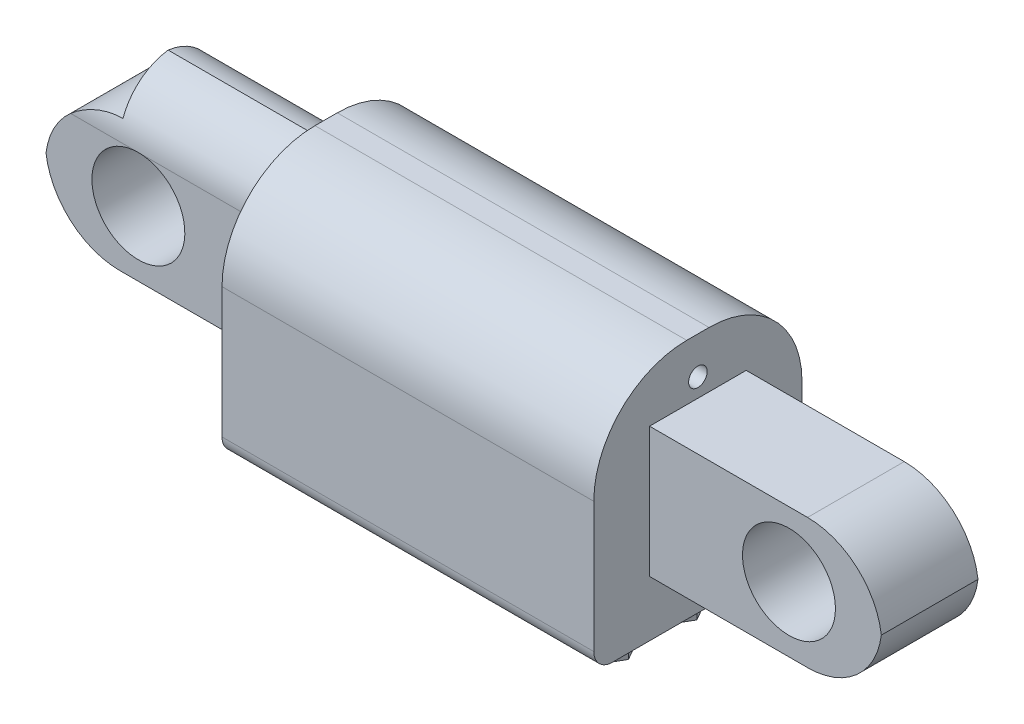
SolidWorks part; units mm, degrees
material "PLA"
ref_plane "Front" through (0, 0, 0) normal (0, 0, 1) x (1, 0, 0)
ref_plane "Top" through (0, 0, 0) normal (0, 1, 0) x (1, 0, 0)
ref_plane "Right" through (0, 0, 0) normal (1, 0, 0) x (0, 0, -1)
sketch "Sketch1" plane through (0, 0, 0) normal (0, 0, 1) x (1, 0, 0)
  line L1 (-6.35, 4.445) -> (9.525, 4.445)
  line L2 (-6.35, 4.445) -> (-6.35, -4.445)
  line L3 (-6.35, -4.445) -> (9.525, -4.445)
  line L4 (9.525, 4.445) -> (9.525, -4.445)
  circle A0 centre (0, 0) radius 3.175
  dimension "D1" = 6.35
  dimension "D2" = 6.35
  dimension "D3" = 4.445
  dimension "D4" = 4.445
  dimension "D5" = 15.875
extrude "Boss-Extrude1" add sketch "Sketch1" along normal blind 6.604
fillet "Fillet1" radius 5.08 2 edges at (-6.35, -4.445, 3.302) (-6.35, 4.445, 3.302)
sketch "Sketch2" plane through (9.525, 0, 0) normal (1, 0, 0) x (0, 0, -1)
  line L0 (-10.414, -8.255) -> (3.81, -8.255)
  line L1 (3.81, -8.255) -> (3.81, 8.255)
  line L2 (3.81, 8.255) -> (-10.414, 8.255)
  line L3 (-10.414, 8.255) -> (-10.414, -8.255)
  line L4 (0, -4.445) -> (0, 4.445)
  line L5 (0, 4.445) -> (-6.604, 4.445)
  line L6 (-6.604, 4.445) -> (-6.604, -4.445)
  line L7 (-6.604, -4.445) -> (0, -4.445)
  line L8 (0, -4.445) -> (0, 4.445)
  line L9 (0, 4.445) -> (-6.604, 4.445)
  line L10 (-6.604, 4.445) -> (-6.604, -4.445)
  line L11 (-6.604, -4.445) -> (0, -4.445)
  line M5 (0, -4.445) -> (0, 4.445)
  line M6 (0, 4.445) -> (-6.604, 4.445)
  line M7 (-6.604, 4.445) -> (-6.604, -4.445)
  line M8 (-6.604, -4.445) -> (0, -4.445)
  dimension "D1" = 0
  dimension "D2" = 3.81
extrude "Boss-Extrude2" add sketch "Sketch2" along normal blind 25.4 separate body contours L2 L3 L0 L1 M5 M8 M7 M6 | M8 M5 M6 M7 region at (9.525, 0, 10.1961) region at (9.525, 0, 3.302)
ref_plane "Plane1" through (22.225, 0, 0) normal (-1, 0, 0) x (0, 0, 1)
mirror "Mirror7" about plane through (22.225, 0, 0) normal (-1, 0, 0) of bodies 101
fillet "Fillet3" radius 6.35 2 edges at (22.225, 8.255, -3.81) (22.225, 8.255, 10.414)
sketch "Sketch3" plane through (0, 4.445, 0) normal (0, 1, 0) x (1, 0, 0)
  line L4 (9.525, 0) -> (-1.27, 0)
  line L5 (-1.27, 0) -> (-1.27, -6.604)
  line L6 (-1.27, -6.604) -> (9.525, -6.604)
  line L7 (9.525, -6.604) -> (9.525, 0)
  line L12 (9.525, 0) -> (-1.27, 0)
  line L13 (-1.27, 0) -> (-1.27, -6.604)
  line L14 (-1.27, -6.604) -> (9.525, -6.604)
  line L15 (9.525, -6.604) -> (9.525, 0)
  dimension "D1" = 0
extrude "Boss-Extrude3" add sketch "Sketch3" along normal blind 2.54
sketch "Sketch4" plane through (-1.27, 0, 0) normal (-1, 0, 0) x (0, 0, 1)
  line L8 (6.604, 6.985) -> (6.604, 4.445) construction
  line L9 (0, 4.445) -> (6.604, 4.445) construction
  circle A0 centre (3.302, 5.715) radius 0.635
  dimension "D1" = 1.27
  dimension "D2" = 1.27
  dimension "D3" = 3.302
extrude "Cut-Extrude1" cut sketch "Sketch4" against normal through all
fillet "Fillet5" radius 3.81 2 edges at (4.1275, 6.985, 6.604) (4.1275, 6.985, 0)
fillet "Fillet6" radius 1.27 2 edges at (22.225, -8.255, -3.81) (22.225, -8.255, 10.414)
sketch "Sketch5" plane through (0, -8.255, 0) normal (0, -1, 0) x (1, 0, 0)
  line L0 (34.925, 2.667) -> (34.925, 3.937) construction
  line L1 (34.925, 9.144) -> (9.525, 9.144)
  line L2 (34.925, 9.144) -> (34.925, -2.54)
  line L3 (34.925, -2.54) -> (9.525, -2.54)
  line L4 (9.525, 9.144) -> (9.525, -2.54)
  line L5 (33.02, 6.9443) -> (34.29, 6.9443)
  line L6 (34.29, 6.9443) -> (34.925, 8.0441)
  line L7 (34.925, 8.0441) -> (34.29, 9.144)
  line L8 (34.29, 9.144) -> (33.02, 9.144)
  line L9 (33.02, 9.144) -> (32.385, 8.0441)
  line L10 (32.385, 8.0441) -> (33.02, 6.9443)
  line L11 (30.48, 6.9443) -> (31.75, 6.9443)
  line L12 (31.75, 6.9443) -> (32.385, 8.0441)
  line L13 (32.385, 8.0441) -> (31.75, 9.144)
  line L14 (31.75, 9.144) -> (30.48, 9.144)
  line L15 (30.48, 9.144) -> (29.845, 8.0441)
  line L16 (29.845, 8.0441) -> (30.48, 6.9443)
  line L17 (27.94, 6.9443) -> (29.21, 6.9443)
  line L18 (29.21, 6.9443) -> (29.845, 8.0441)
  line L19 (29.845, 8.0441) -> (29.21, 9.144)
  line L20 (29.21, 9.144) -> (27.94, 9.144)
  line L21 (27.94, 9.144) -> (27.305, 8.0441)
  line L22 (27.305, 8.0441) -> (27.94, 6.9443)
  line L23 (25.4, 6.9443) -> (26.67, 6.9443)
  line L24 (26.67, 6.9443) -> (27.305, 8.0441)
  line L25 (27.305, 8.0441) -> (26.67, 9.144)
  line L26 (26.67, 9.144) -> (25.4, 9.144)
  line L27 (25.4, 9.144) -> (24.765, 8.0441)
  line L28 (24.765, 8.0441) -> (25.4, 6.9443)
  line L29 (22.86, 6.9443) -> (24.13, 6.9443)
  line L30 (24.13, 6.9443) -> (24.765, 8.0441)
  line L31 (24.765, 8.0441) -> (24.13, 9.144)
  line L32 (24.13, 9.144) -> (22.86, 9.144)
  line L33 (22.86, 9.144) -> (22.225, 8.0441)
  line L34 (22.225, 8.0441) -> (22.86, 6.9443)
  line L35 (20.32, 6.9443) -> (21.59, 6.9443)
  line L36 (21.59, 6.9443) -> (22.225, 8.0441)
  line L37 (22.225, 8.0441) -> (21.59, 9.144)
  line L38 (21.59, 9.144) -> (20.32, 9.144)
  line L39 (20.32, 9.144) -> (19.685, 8.0441)
  line L40 (19.685, 8.0441) -> (20.32, 6.9443)
  line L41 (17.78, 6.9443) -> (19.05, 6.9443)
  line L42 (19.05, 6.9443) -> (19.685, 8.0441)
  line L43 (19.685, 8.0441) -> (19.05, 9.144)
  line L44 (19.05, 9.144) -> (17.78, 9.144)
  line L45 (17.78, 9.144) -> (17.145, 8.0441)
  line L46 (17.145, 8.0441) -> (17.78, 6.9443)
  line L47 (15.24, 6.9443) -> (16.51, 6.9443)
  line L48 (16.51, 6.9443) -> (17.145, 8.0441)
  line L49 (17.145, 8.0441) -> (16.51, 9.144)
  line L50 (16.51, 9.144) -> (15.24, 9.144)
  line L51 (15.24, 9.144) -> (14.605, 8.0441)
  line L52 (14.605, 8.0441) -> (15.24, 6.9443)
  line L53 (12.7, 6.9443) -> (13.97, 6.9443)
  line L54 (13.97, 6.9443) -> (14.605, 8.0441)
  line L55 (14.605, 8.0441) -> (13.97, 9.144)
  line L56 (13.97, 9.144) -> (12.7, 9.144)
  line L57 (12.7, 9.144) -> (12.065, 8.0441)
  line L58 (12.065, 8.0441) -> (12.7, 6.9443)
  line L59 (10.16, 6.9443) -> (11.43, 6.9443)
  line L60 (11.43, 6.9443) -> (12.065, 8.0441)
  line L61 (12.065, 8.0441) -> (11.43, 9.144)
  line L62 (11.43, 9.144) -> (10.16, 9.144)
  line L63 (10.16, 9.144) -> (9.525, 8.0441)
  line L64 (9.525, 8.0441) -> (10.16, 6.9443)
  line L65 (30.48, 4.6075) -> (31.75, 4.6075)
  line L66 (31.75, 4.6075) -> (32.385, 5.7073)
  line L67 (32.385, 5.7073) -> (31.75, 6.8072)
  line L68 (31.75, 6.8072) -> (30.48, 6.8072)
  line L69 (30.48, 6.8072) -> (29.845, 5.7073)
  line L70 (29.845, 5.7073) -> (30.48, 4.6075)
  line L71 (27.94, 4.6075) -> (29.21, 4.6075)
  line L72 (29.21, 4.6075) -> (29.845, 5.7073)
  line L73 (29.845, 5.7073) -> (29.21, 6.8072)
  line L74 (29.21, 6.8072) -> (27.94, 6.8072)
  line L75 (27.94, 6.8072) -> (27.305, 5.7073)
  line L76 (27.305, 5.7073) -> (27.94, 4.6075)
  line L77 (25.4, 4.6075) -> (26.67, 4.6075)
  line L78 (26.67, 4.6075) -> (27.305, 5.7073)
  line L79 (27.305, 5.7073) -> (26.67, 6.8072)
  line L80 (26.67, 6.8072) -> (25.4, 6.8072)
  line L81 (25.4, 6.8072) -> (24.765, 5.7073)
  line L82 (24.765, 5.7073) -> (25.4, 4.6075)
  line L83 (22.86, 4.6075) -> (24.13, 4.6075)
  line L84 (24.13, 4.6075) -> (24.765, 5.7073)
  line L85 (24.765, 5.7073) -> (24.13, 6.8072)
  line L86 (24.13, 6.8072) -> (22.86, 6.8072)
  line L87 (22.86, 6.8072) -> (22.225, 5.7073)
  line L88 (22.225, 5.7073) -> (22.86, 4.6075)
  line L89 (20.32, 4.6075) -> (21.59, 4.6075)
  line L90 (21.59, 4.6075) -> (22.225, 5.7073)
  line L91 (22.225, 5.7073) -> (21.59, 6.8072)
  line L92 (21.59, 6.8072) -> (20.32, 6.8072)
  line L93 (20.32, 6.8072) -> (19.685, 5.7073)
  line L94 (19.685, 5.7073) -> (20.32, 4.6075)
  line L95 (17.78, 4.6075) -> (19.05, 4.6075)
  line L96 (19.05, 4.6075) -> (19.685, 5.7073)
  line L97 (19.685, 5.7073) -> (19.05, 6.8072)
  line L98 (19.05, 6.8072) -> (17.78, 6.8072)
  line L99 (17.78, 6.8072) -> (17.145, 5.7073)
  line L100 (17.145, 5.7073) -> (17.78, 4.6075)
  line L101 (15.24, 4.6075) -> (16.51, 4.6075)
  line L102 (16.51, 4.6075) -> (17.145, 5.7073)
  line L103 (17.145, 5.7073) -> (16.51, 6.8072)
  line L104 (16.51, 6.8072) -> (15.24, 6.8072)
  line L105 (15.24, 6.8072) -> (14.605, 5.7073)
  line L106 (14.605, 5.7073) -> (15.24, 4.6075)
  line L107 (12.7, 4.6075) -> (13.97, 4.6075)
  line L108 (13.97, 4.6075) -> (14.605, 5.7073)
  line L109 (14.605, 5.7073) -> (13.97, 6.8072)
  line L110 (13.97, 6.8072) -> (12.7, 6.8072)
  line L111 (12.7, 6.8072) -> (12.065, 5.7073)
  line L112 (12.065, 5.7073) -> (12.7, 4.6075)
  line L113 (10.16, 4.6075) -> (11.43, 4.6075)
  line L114 (11.43, 4.6075) -> (12.065, 5.7073)
  line L115 (12.065, 5.7073) -> (11.43, 6.8072)
  line L116 (11.43, 6.8072) -> (10.16, 6.8072)
  line L117 (10.16, 6.8072) -> (9.525, 5.7073)
  line L118 (9.525, 5.7073) -> (10.16, 4.6075)
  line L119 (30.48, 2.2707) -> (31.75, 2.2707)
  line L120 (31.75, 2.2707) -> (32.385, 3.3705)
  line L121 (32.385, 3.3705) -> (31.75, 4.4704)
  line L122 (31.75, 4.4704) -> (30.48, 4.4704)
  line L123 (30.48, 4.4704) -> (29.845, 3.3705)
  line L124 (29.845, 3.3705) -> (30.48, 2.2707)
  line L125 (27.94, 2.2707) -> (29.21, 2.2707)
  line L126 (29.21, 2.2707) -> (29.845, 3.3705)
  line L127 (29.845, 3.3705) -> (29.21, 4.4704)
  line L128 (29.21, 4.4704) -> (27.94, 4.4704)
  line L129 (27.94, 4.4704) -> (27.305, 3.3705)
  line L130 (27.305, 3.3705) -> (27.94, 2.2707)
  line L131 (25.4, 2.2707) -> (26.67, 2.2707)
  line L132 (26.67, 2.2707) -> (27.305, 3.3705)
  line L133 (27.305, 3.3705) -> (26.67, 4.4704)
  line L134 (26.67, 4.4704) -> (25.4, 4.4704)
  line L135 (25.4, 4.4704) -> (24.765, 3.3705)
  line L136 (24.765, 3.3705) -> (25.4, 2.2707)
  line L137 (22.86, 2.2707) -> (24.13, 2.2707)
  line L138 (24.13, 2.2707) -> (24.765, 3.3705)
  line L139 (24.765, 3.3705) -> (24.13, 4.4704)
  line L140 (24.13, 4.4704) -> (22.86, 4.4704)
  line L141 (22.86, 4.4704) -> (22.225, 3.3705)
  line L142 (22.225, 3.3705) -> (22.86, 2.2707)
  line L143 (20.32, 2.2707) -> (21.59, 2.2707)
  line L144 (21.59, 2.2707) -> (22.225, 3.3705)
  line L145 (22.225, 3.3705) -> (21.59, 4.4704)
  line L146 (21.59, 4.4704) -> (20.32, 4.4704)
  line L147 (20.32, 4.4704) -> (19.685, 3.3705)
  line L148 (19.685, 3.3705) -> (20.32, 2.2707)
  line L149 (17.78, 2.2707) -> (19.05, 2.2707)
  line L150 (19.05, 2.2707) -> (19.685, 3.3705)
  line L151 (19.685, 3.3705) -> (19.05, 4.4704)
  line L152 (19.05, 4.4704) -> (17.78, 4.4704)
  line L153 (17.78, 4.4704) -> (17.145, 3.3705)
  line L154 (17.145, 3.3705) -> (17.78, 2.2707)
  line L155 (15.24, 2.2707) -> (16.51, 2.2707)
  line L156 (16.51, 2.2707) -> (17.145, 3.3705)
  line L157 (17.145, 3.3705) -> (16.51, 4.4704)
  line L158 (16.51, 4.4704) -> (15.24, 4.4704)
  line L159 (15.24, 4.4704) -> (14.605, 3.3705)
  line L160 (14.605, 3.3705) -> (15.24, 2.2707)
  line L161 (12.7, 2.2707) -> (13.97, 2.2707)
  line L162 (13.97, 2.2707) -> (14.605, 3.3705)
  line L163 (14.605, 3.3705) -> (13.97, 4.4704)
  line L164 (13.97, 4.4704) -> (12.7, 4.4704)
  line L165 (12.7, 4.4704) -> (12.065, 3.3705)
  line L166 (12.065, 3.3705) -> (12.7, 2.2707)
  line L167 (10.16, 2.2707) -> (11.43, 2.2707)
  line L168 (11.43, 2.2707) -> (12.065, 3.3705)
  line L169 (12.065, 3.3705) -> (11.43, 4.4704)
  line L170 (11.43, 4.4704) -> (10.16, 4.4704)
  line L171 (10.16, 4.4704) -> (9.525, 3.3705)
  line L172 (9.525, 3.3705) -> (10.16, 2.2707)
  line L173 (30.48, -0.0661) -> (31.75, -0.0661)
  line L174 (31.75, -0.0661) -> (32.385, 1.0337)
  line L175 (32.385, 1.0337) -> (31.75, 2.1336)
  line L176 (31.75, 2.1336) -> (30.48, 2.1336)
  line L177 (30.48, 2.1336) -> (29.845, 1.0337)
  line L178 (29.845, 1.0337) -> (30.48, -0.0661)
  line L179 (27.94, -0.0661) -> (29.21, -0.0661)
  line L180 (29.21, -0.0661) -> (29.845, 1.0337)
  line L181 (29.845, 1.0337) -> (29.21, 2.1336)
  line L182 (29.21, 2.1336) -> (27.94, 2.1336)
  line L183 (27.94, 2.1336) -> (27.305, 1.0337)
  line L184 (27.305, 1.0337) -> (27.94, -0.0661)
  line L185 (25.4, -0.0661) -> (26.67, -0.0661)
  line L186 (26.67, -0.0661) -> (27.305, 1.0337)
  line L187 (27.305, 1.0337) -> (26.67, 2.1336)
  line L188 (26.67, 2.1336) -> (25.4, 2.1336)
  line L189 (25.4, 2.1336) -> (24.765, 1.0337)
  line L190 (24.765, 1.0337) -> (25.4, -0.0661)
  line L191 (22.86, -0.0661) -> (24.13, -0.0661)
  line L192 (24.13, -0.0661) -> (24.765, 1.0337)
  line L193 (24.765, 1.0337) -> (24.13, 2.1336)
  line L194 (24.13, 2.1336) -> (22.86, 2.1336)
  line L195 (22.86, 2.1336) -> (22.225, 1.0337)
  line L196 (22.225, 1.0337) -> (22.86, -0.0661)
  line L197 (20.32, -0.0661) -> (21.59, -0.0661)
  line L198 (21.59, -0.0661) -> (22.225, 1.0337)
  line L199 (22.225, 1.0337) -> (21.59, 2.1336)
  line L200 (21.59, 2.1336) -> (20.32, 2.1336)
  line L201 (20.32, 2.1336) -> (19.685, 1.0337)
  line L202 (19.685, 1.0337) -> (20.32, -0.0661)
  line L203 (17.78, -0.0661) -> (19.05, -0.0661)
  line L204 (19.05, -0.0661) -> (19.685, 1.0337)
  line L205 (19.685, 1.0337) -> (19.05, 2.1336)
  line L206 (19.05, 2.1336) -> (17.78, 2.1336)
  line L207 (17.78, 2.1336) -> (17.145, 1.0337)
  line L208 (17.145, 1.0337) -> (17.78, -0.0661)
  line L209 (15.24, -0.0661) -> (16.51, -0.0661)
  line L210 (16.51, -0.0661) -> (17.145, 1.0337)
  line L211 (17.145, 1.0337) -> (16.51, 2.1336)
  line L212 (16.51, 2.1336) -> (15.24, 2.1336)
  line L213 (15.24, 2.1336) -> (14.605, 1.0337)
  line L214 (14.605, 1.0337) -> (15.24, -0.0661)
  line L215 (12.7, -0.0661) -> (13.97, -0.0661)
  line L216 (13.97, -0.0661) -> (14.605, 1.0337)
  line L217 (14.605, 1.0337) -> (13.97, 2.1336)
  line L218 (13.97, 2.1336) -> (12.7, 2.1336)
  line L219 (12.7, 2.1336) -> (12.065, 1.0337)
  line L220 (12.065, 1.0337) -> (12.7, -0.0661)
  line L221 (10.16, -0.0661) -> (11.43, -0.0661)
  line L222 (11.43, -0.0661) -> (12.065, 1.0337)
  line L223 (12.065, 1.0337) -> (11.43, 2.1336)
  line L224 (11.43, 2.1336) -> (10.16, 2.1336)
  line L225 (10.16, 2.1336) -> (9.525, 1.0337)
  line L226 (9.525, 1.0337) -> (10.16, -0.0661)
  line L227 (30.48, -2.4029) -> (31.75, -2.4029)
  line L228 (31.75, -2.4029) -> (32.385, -1.3031)
  line L229 (32.385, -1.3031) -> (31.75, -0.2032)
  line L230 (31.75, -0.2032) -> (30.48, -0.2032)
  line L231 (30.48, -0.2032) -> (29.845, -1.3031)
  line L232 (29.845, -1.3031) -> (30.48, -2.4029)
  line L233 (27.94, -2.4029) -> (29.21, -2.4029)
  line L234 (29.21, -2.4029) -> (29.845, -1.3031)
  line L235 (29.845, -1.3031) -> (29.21, -0.2032)
  line L236 (29.21, -0.2032) -> (27.94, -0.2032)
  line L237 (27.94, -0.2032) -> (27.305, -1.3031)
  line L238 (27.305, -1.3031) -> (27.94, -2.4029)
  line L239 (25.4, -2.4029) -> (26.67, -2.4029)
  line L240 (26.67, -2.4029) -> (27.305, -1.3031)
  line L241 (27.305, -1.3031) -> (26.67, -0.2032)
  line L242 (26.67, -0.2032) -> (25.4, -0.2032)
  line L243 (25.4, -0.2032) -> (24.765, -1.3031)
  line L244 (24.765, -1.3031) -> (25.4, -2.4029)
  line L245 (22.86, -2.4029) -> (24.13, -2.4029)
  line L246 (24.13, -2.4029) -> (24.765, -1.3031)
  line L247 (24.765, -1.3031) -> (24.13, -0.2032)
  line L248 (24.13, -0.2032) -> (22.86, -0.2032)
  line L249 (22.86, -0.2032) -> (22.225, -1.3031)
  line L250 (22.225, -1.3031) -> (22.86, -2.4029)
  line L251 (20.32, -2.4029) -> (21.59, -2.4029)
  line L252 (21.59, -2.4029) -> (22.225, -1.3031)
  line L253 (22.225, -1.3031) -> (21.59, -0.2032)
  line L254 (21.59, -0.2032) -> (20.32, -0.2032)
  line L255 (20.32, -0.2032) -> (19.685, -1.3031)
  line L256 (19.685, -1.3031) -> (20.32, -2.4029)
  line L257 (17.78, -2.4029) -> (19.05, -2.4029)
  line L258 (19.05, -2.4029) -> (19.685, -1.3031)
  line L259 (19.685, -1.3031) -> (19.05, -0.2032)
  line L260 (19.05, -0.2032) -> (17.78, -0.2032)
  line L261 (17.78, -0.2032) -> (17.145, -1.3031)
  line L262 (17.145, -1.3031) -> (17.78, -2.4029)
  line L263 (15.24, -2.4029) -> (16.51, -2.4029)
  line L264 (16.51, -2.4029) -> (17.145, -1.3031)
  line L265 (17.145, -1.3031) -> (16.51, -0.2032)
  line L266 (16.51, -0.2032) -> (15.24, -0.2032)
  line L267 (15.24, -0.2032) -> (14.605, -1.3031)
  line L268 (14.605, -1.3031) -> (15.24, -2.4029)
  line L269 (12.7, -2.4029) -> (13.97, -2.4029)
  line L270 (13.97, -2.4029) -> (14.605, -1.3031)
  line L271 (14.605, -1.3031) -> (13.97, -0.2032)
  line L272 (13.97, -0.2032) -> (12.7, -0.2032)
  line L273 (12.7, -0.2032) -> (12.065, -1.3031)
  line L274 (12.065, -1.3031) -> (12.7, -2.4029)
  line L275 (10.16, -2.4029) -> (11.43, -2.4029)
  line L276 (11.43, -2.4029) -> (12.065, -1.3031)
  line L277 (12.065, -1.3031) -> (11.43, -0.2032)
  line L278 (11.43, -0.2032) -> (10.16, -0.2032)
  line L279 (10.16, -0.2032) -> (9.525, -1.3031)
  line L280 (9.525, -1.3031) -> (10.16, -2.4029)
  line L281 (33.02, 4.6075) -> (34.29, 4.6075)
  line L282 (34.29, 4.6075) -> (34.925, 5.7073)
  line L283 (34.925, 5.7073) -> (34.29, 6.8072)
  line L284 (34.29, 6.8072) -> (33.02, 6.8072)
  line L285 (33.02, 6.8072) -> (32.385, 5.7073)
  line L286 (32.385, 5.7073) -> (33.02, 4.6075)
  line L287 (33.02, 2.2707) -> (34.29, 2.2707)
  line L288 (34.29, 2.2707) -> (34.925, 3.3705)
  line L289 (34.925, 3.3705) -> (34.29, 4.4704)
  line L290 (34.29, 4.4704) -> (33.02, 4.4704)
  line L291 (33.02, 4.4704) -> (32.385, 3.3705)
  line L292 (32.385, 3.3705) -> (33.02, 2.2707)
  line L293 (33.02, -0.0661) -> (34.29, -0.0661)
  line L294 (34.29, -0.0661) -> (34.925, 1.0337)
  line L295 (34.925, 1.0337) -> (34.29, 2.1336)
  line L296 (34.29, 2.1336) -> (33.02, 2.1336)
  line L297 (33.02, 2.1336) -> (32.385, 1.0337)
  line L298 (32.385, 1.0337) -> (33.02, -0.0661)
  line L299 (33.02, -2.4029) -> (34.29, -2.4029)
  line L300 (34.29, -2.4029) -> (34.925, -1.3031)
  line L301 (34.925, -1.3031) -> (34.29, -0.2032)
  line L302 (34.29, -0.2032) -> (33.02, -0.2032)
  line L303 (33.02, -0.2032) -> (32.385, -1.3031)
  line L304 (32.385, -1.3031) -> (33.02, -2.4029)
  circle A0 centre (33.655, 8.0441) radius 1.0999 construction
  dimension "D1" = 2.54
  dimension "D2" = 10
  dimension "D3" = 5
extrude "Boss-Extrude7" add sketch "Sketch5" along normal blind 0.381 contours L9 L10 L5 L6 L7 L1 | L21 L22 L17 L18 L19 L1 | L33 L34 L29 L30 L31 L1 | L45 L46 L41 L42 L43 L1 | L57 L58 L53 L54 L55 L1 | L65 L66 L67 L68 L69 L70 | L77 L78 L79 L80 L81 L82 | L89 L90 L91 L92 L93 L94 | L101 L102 L103 L104 L105 L106 | L113 L114 L115 L116 L117 L118 | L287 L288 L289 L290 L291 L292 | L125 L126 L127 L128 L129 L130 | L137 L138 L139 L140 L141 L142 | L149 L150 L151 L152 L153 L154 | L161 L162 L163 L164 L165 L166 | L173 L174 L175 L176 L177 L178 | L185 L186 L187 L188 L189 L190 | L197 L198 L199 L200 L201 L202 | L209 L210 L211 L212 L213 L214 | L221 L222 L223 L224 L225 L226 | L299 L300 L301 L302 L303 L304 | L233 L234 L235 L236 L237 L238 | L245 L246 L247 L248 L249 L250 | L257 L258 L259 L260 L261 L262 | L269 L270 L271 L272 L273 L274 region at (33.655, -8.255, 8.0441) region at (28.575, -8.255, 8.0441) region at (23.495, -8.255, 8.0441) region at (18.415, -8.255, 8.0441) region at (13.335, -8.255, 8.0441)
